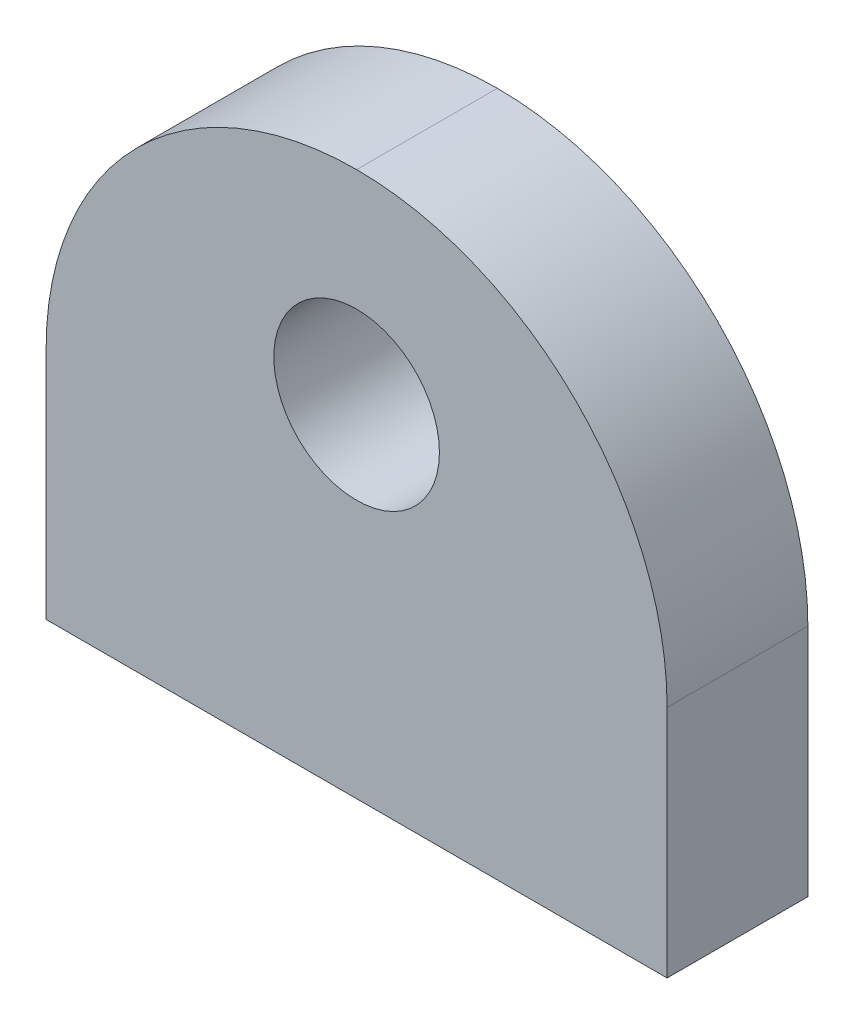
SolidWorks part; units mm, degrees
ref_plane "Alzado" through (0, 0, 0) normal (0, 0, 1) x (1, 0, 0)
ref_plane "Planta" through (0, 0, 0) normal (0, 1, 0) x (1, 0, 0)
ref_plane "Vista lateral" through (0, 0, 0) normal (1, 0, 0) x (0, 0, -1)
sketch "Croquis1" plane through (0, 0, 0) normal (0, 0, 1) x (1, 0, 0)
  line L0 (0, 0) -> (30, 0)
  line L1 (0, 0) -> (0, 26.3226)
  line L2 (0, 26.3226) -> (30, 26.3226)
  line L3 (30, 26.3226) -> (30, 0)
  dimension "D1" = 30
extrude "Saliente-Extruir1" add sketch "Croquis1" along normal blind 6.8
fillet "Redondeo1" radius 15 2 edges at (0, 26.3226, 3.4) (30, 26.3226, 3.4)
sketch "Croquis2" plane through (0, 0, 6.8) normal (0, 0, 1) x (1, 0, 0)
  circle A2 centre (15, 16.4856) radius 4
  dimension "D1" = 8
extrude "Cortar-Extruir1" cut sketch "Croquis2" against normal up to next
